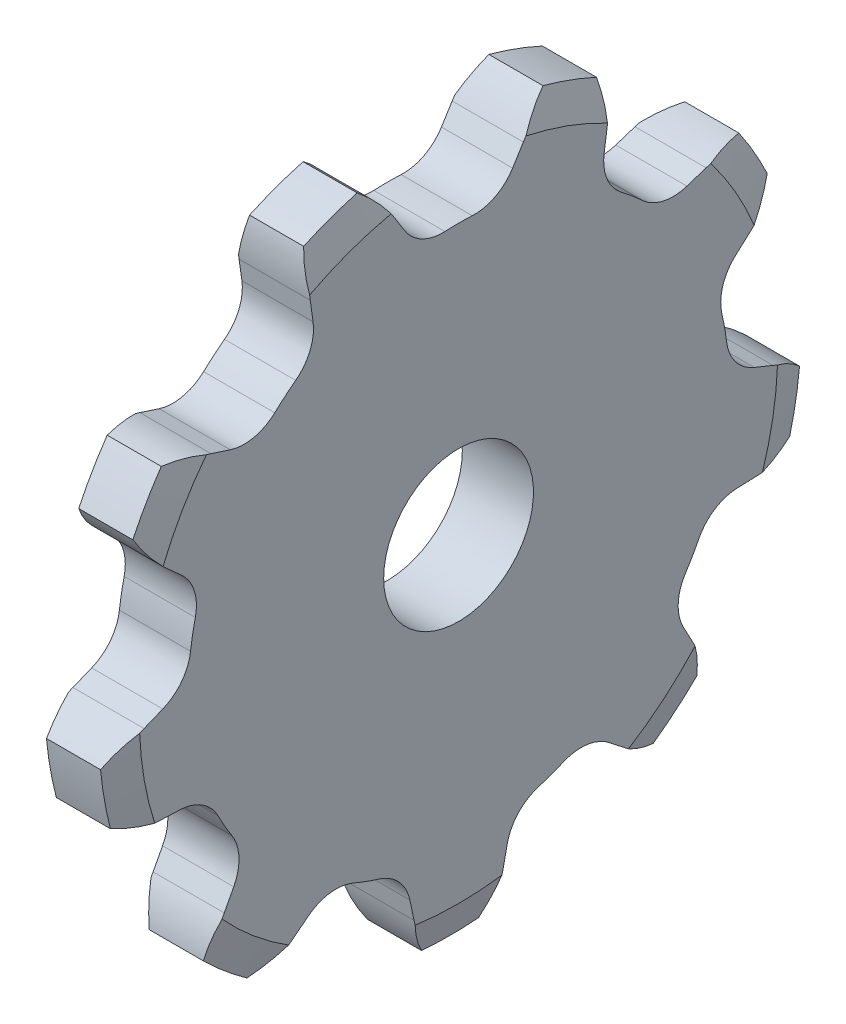
SolidWorks part; units mm, degrees
ref_plane "Plane1" through (0, 0, 0) normal (0, 0, 1) x (1, 0, 0)
ref_plane "Plane2" through (0, 0, 0) normal (0, 1, 0) x (1, 0, 0)
ref_plane "Plane3" through (0, 0, 0) normal (1, 0, 0) x (0, 0, -1)
sketch "Clipboard" plane through (0, 0, 0) normal (0, 1, 0) x (1, 0, 0)
  line L0 (0, 0) -> (75.2619, -11.9203)
  line L1 (-15, 0) -> (100, 0) construction
  line L2 (0, 0) -> (-2.1039, 2.3779)
  line L3 (0, 0) -> (-11.863, 4.5341)
  line L4 (0, 0) -> (8.5297, 1.351)
  line L5 (0, 0) -> (-71.3958, -26.6285)
  line L6 (0, 0) -> (-20.0029, -13.496)
  line L7 (-2.1039, 2.3779) -> (14.2981, 76.7917)
  line L8 (-76.2, 54.61) -> (-19.7358, 54.61)
  line L9 (-66.6514, 23.5599) -> (-48.0177, 27.5206)
  line L10 (-76.2, 71.12) -> (35.1969, 71.12)
  line L11 (0, 0) -> (-25.4, 0)
  line L12 (-76.2, 101.6) -> (-47.498, 101.6)
  circle A0 centre (0, 0) radius 19.05
  circle A1 centre (0, 0) radius 25.4
  circle A2 centre (0, 0) radius 25.4
  dimension "Num_teeth" = 9
  dimension "Pitch_radius" = 111.3969
  dimension "F" = 28.702
  dimension "H" = 19.05
  dimension "Thickness" = 24.13
sketch "BasProSke" plane through (0, 0, 0) normal (0, 1, 0) x (1, 0, 0)
  line L0 (-10, 0) -> (60, 0) construction
  line L1 (0, 0) -> (0, 108.2234)
  line L2 (0, 0) -> (24.13, 0)
  line L3 (24.13, 0) -> (24.13, 108.2234)
  line L4 (21.2344, 119.0299) -> (2.8956, 119.0299)
  line L5 (0, 108.2234) -> (2.8956, 119.0299)
  line L6 (24.13, 108.2234) -> (21.2344, 119.0299)
  dimension "Thickness" = 24.13
  dimension "Diameter" = 238.0598
  dimension "D1" = 15
  dimension "D2" = 15
revolve "Base-Revolve" add sketch "BasProSke" angle 360 about L0
sketch "TooCutSke" plane through (0, 0, 0) normal (1, 0, 0) x (0, 0, -1)
  line L0 (-18.3254, 98.6123) -> (-21.9596, 104.4283)
  line L1 (0, 0) -> (0, 107) construction
  line L2 (3.81, 0) -> (3.81, 141.3423) construction
  line L3 (18.3254, 98.6123) -> (21.9596, 104.4283)
  line L4 (44.0158, 120.9324) -> (48.3595, 132.8665)
  line L5 (3.81, 115.7694) -> (59.0408, 81.2573) construction
  line L6 (-44.0158, 120.9324) -> (-48.3595, 132.8665)
  arc A0 (4.6306, 91.4678) -> (-4.6306, 91.4678) centre (0, 0) ccw
  arc A1 (4.6306, 91.4678) -> (18.3254, 98.6123) centre (5.4011, 106.6883) ccw
  arc A2 (-4.6306, 91.4678) -> (-18.3254, 98.6123) centre (-5.4011, 106.6883) cw
  circle A3 centre (0, 0) radius 111.3969 construction
  circle A4 centre (3.81, 111.3318) radius 19.05 construction
  arc A5 (21.9596, 104.4283) -> (44.0158, 120.9324) centre (54.2702, 84.2383) cw
  arc A6 (-21.9596, 104.4283) -> (-44.0158, 120.9324) centre (-54.2702, 84.2383) ccw
  arc A7 (48.3595, 132.8665) -> (-48.3595, 132.8665) centre (0, 0) ccw
  dimension "Pitch_radius" = 111.3969
  dimension "R" = 15.24
  dimension "H" = 19.05
  dimension "Ag" = 64
  dimension "Angle" = 40
extrude "ToothCut" cut sketch "TooCutSke" along normal through all
pattern_circular "TeethCuts" count 9 every 40 about axis through (-10, 0, 0) along (1, 0, 0) of "ToothCut"
sketch "HubNeaOneSke" plane through (0, 0, 0) normal (-1, 0, 0) x (0, 0, 1)
  circle A0 centre (0, 0) radius 25.4
  dimension "Diameter" = 50.8
extrude "HubNearOne" [suppressed] add sketch "HubNeaOneSke" along normal blind 52.0701
sketch "HubNeaBotSke" plane through (0, 0, 0) normal (-1, 0, 0) x (0, 0, 1)
  circle A0 centre (0, 0) radius 25.4
  dimension "Diameter" = 50.8
extrude "HubNearBoth" [suppressed] add sketch "HubNeaBotSke" along normal blind 26.035
ref_plane "FarPln" through (24.13, 0, 0) normal (1, 0, 0) x (0, 0, -1)
sketch "HubFarSke" plane through (24.13, 0, 0) normal (1, 0, 0) x (0, 0, -1)
  circle A0 centre (0, 0) radius 25.4
  dimension "Diameter" = 50.8
extrude "HubFar" [suppressed] add sketch "HubFarSke" along normal blind 26.035
sketch "BorSke" plane through (0, 0, 0) normal (1, 0, 0) x (0, 0, -1)
  circle A0 centre (0, 0) radius 25.4
  dimension "Diameter" = 50.8
extrude "Bore" cut sketch "BorSke" along normal mid plane 152.4001
sketch "KeySke" plane through (0, 0, 0) normal (1, 0, 0) x (0, 0, -1)
  line L0 (-6.35, 0) -> (-6.35, 31.0642)
  line L1 (-6.35, 31.0642) -> (6.35, 31.0642)
  line L2 (6.35, 31.0642) -> (6.35, 0)
  line L3 (0, 0) -> (0, 34) construction
  line L4 (-6.35, 0) -> (6.35, 0)
  dimension "Width" = 12.7
extrude "Keyway" [suppressed] cut sketch "KeySke" along normal mid plane 152.4001
pattern_circular "Keyway2" [suppressed] count 2 every 90 about axis through (-10, 0, 0) along (1, 0, 0) reverse direction yes
equation "\"Thickness@Clipboard\" = \"Width@Clipboard\" * 0.95"
equation "\"H@Clipboard\" = \"Diameter@Clipboard\" / 2.0"
equation "\"OAL@Clipboard\" = \"Thickness@Clipboard\""
equation "\"Pitch_radius@Clipboard\" = ( \"Pitch@Clipboard\" / 2.0) / sin(3.14159265 / \"Num_teeth@Clipboard\" )"
equation "\"MHD@Clipboard\" = (1.0 / tan(3.14159265 / \"Num_teeth@Clipboard\" ) - 0.05) * \"Pitch@Clipboard\" - \"F@Clipboard\""
equation "\"MHD@Clipboard\" = ((sgn( \"MHD@Clipboard\" - \"Hub_dia@Clipboard\" )-1)*( \"MHD@Clipboard\" - \"Hub_dia@Clipboard\" ))/-2+ \"Hub_dia@Clipboard\""
equation "\"OAL@Clipboard\" = ((sgn( \"OAL@Clipboard\" - \"Overall_len@Clipboard\" )+1)*( \"OAL@Clipboard\" - \"Overall_len@Clipboard\" ))/2 + \"Overall_len@Clipboard\" + 0.000002"
equation "\"Num_teeth@TeethCuts\" = int( \"Show_teeth@Clipboard\" ) + 1"
equation "\"Num_teeth@TeethCuts\" = ((sgn( \"Num_teeth@TeethCuts\" - \"Num_teeth@Clipboard\" )-1)*( \"Num_teeth@TeethCuts\" - \"Num_teeth@Clipboard\" ))/-2+ \"Num_teeth@Clipboard\""
equation "\"Num_teeth@TeethCuts\" = ((sgn( \"Num_teeth@TeethCuts\" - 2.0)+1)*( \"Num_teeth@TeethCuts\" - 2.0))/2 +2.0"
equation "\"Angle@TeethCuts\" = 360.0 / \"Num_teeth@Clipboard\""
equation "\"Pitch_radius@TooCutSke\" = \"Pitch_radius@Clipboard\""
equation "\"Cp@TooCutSke\" = 0.05 * \"Pitch@Clipboard\""
equation "\"Rt@TooCutSke\" = 0.5 * \"Pitch@Clipboard\""
equation "\"R@TooCutSke\"  = 0.8 * \"H@Clipboard\""
equation "\"Db@TooCutSke\" = \"Pitch_radius@Clipboard\" - \"H@Clipboard\" - 0.03"
equation "\"Ag@TooCutSke\" =  2.0 * \"Ap@Clipboard\" + 360.0 / \"Num_teeth@Clipboard\""
equation "\"H@TooCutSke\" = \"H@Clipboard\""
equation "\"Angle@TooCutSke\" =  360.0 / \"Num_teeth@Clipboard\""
equation "\"Wf@TooCutSke\" = 0.01 * \"Pitch@Clipboard\" * \"Num_teeth@Clipboard\""
equation "\"Wf@TooCutSke\" = ((sgn( \"Wf@TooCutSke\" - \"H@Clipboard\" * 0.8 )-1)*( \"Wf@TooCutSke\" - \"H@Clipboard\" * 0.8 ))/-2+ \"H@Clipboard\" * 0.8"
equation "\"Diameter@BasProSke\" = (1.0 / tan(3.14159265 / \"Num_teeth@Clipboard\" )) * \"Pitch@Clipboard\" + \"F@Clipboard\""
equation "\"Thickness@BasProSke\"  = \"Thickness@Clipboard\""
equation "\"G1@BasProSke\" =  \"Thickness@Clipboard\" * 0.12"
equation "\"G2@BasProSke\" =   \"Thickness@Clipboard\" * 0.12"
equation "\"MHD@Clipboard\" = ((sgn( \"MHD@Clipboard\" - \"Db@TooCutSke\" * 2.0  )-1)*( \"MHD@Clipboard\" - \"Db@TooCutSke\" * 2.0 ))/-2+ \"Db@TooCutSke\" * 2.0"
equation "\"Diameter@HubNeaOneSke\" = \"MHD@Clipboard\""
equation "\"Length@HubNearOne\" = \"OAL@Clipboard\" - \"Thickness@BasProSke\""
equation "\"Diameter@HubNeaBotSke\" = \"MHD@Clipboard\""
equation "\"Length@HubNearBoth\" = ( \"OAL@Clipboard\" - \"Thickness@BasProSke\" ) / 2.0"
equation "\"Thickness@FarPln\" = \"Thickness@BasProSke\""
equation "\"Diameter@HubFarSke\" = \"MHD@Clipboard\""
equation "\"Length@HubFar\" = ( \"OAL@Clipboard\" - \"Thickness@BasProSke\" ) / 2.0"
equation "\"D1@Bore\" = \"OAL@Clipboard\" * 2.0"
equation "\"D1@Keyway\" = \"OAL@Clipboard\" * 2.0"
equation "\"Offset@KeySke\" = \"T_dim@Clipboard\" - \"Diameter@BorSke\" / 2.0"
